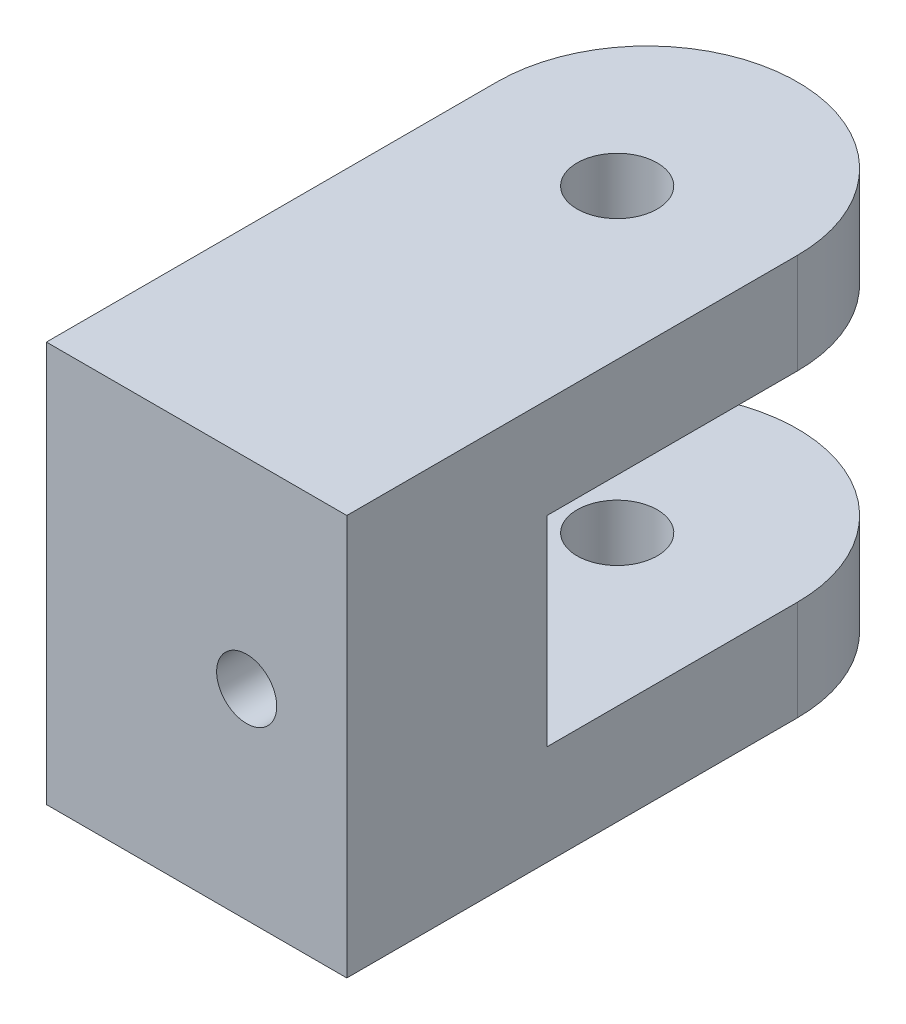
SolidWorks part; units mm, degrees
ref_plane "前视基准面" through (0, 0, 0) normal (0, 0, 1) x (1, 0, 0)
ref_plane "上视基准面" through (0, 0, 0) normal (0, 1, 0) x (1, 0, 0)
ref_plane "右视基准面" through (0, 0, 0) normal (1, 0, 0) x (0, 0, -1)
other "Configuration Table"
sketch "草图1" plane through (0, 0, 0) normal (0, 0, 1) x (1, 0, 0)
  line L1 (0, 0) -> (15, 0)
  line L2 (0, 0) -> (0, 20)
  line L3 (0, 20) -> (15, 20)
  line L4 (15, 0) -> (15, 20)
  point P4 (0, 0)
  dimension "D1" = 15
  dimension "D2" = 20
extrude "凸台-拉伸1" add sketch "草图1" along normal blind 10
sketch "草图2" plane through (0, 0, 0) normal (0, -1, 0) x (1, 0, 0)
  line L6 (0, 0) -> (0, -20)
  line L7 (0, -20) -> (15, -20)
  line L8 (15, -20) -> (15, 0)
  line L9 (15, 0) -> (0, 0)
  circle A0 centre (7.5, -11) radius 2
  dimension "D4" = 4
  dimension "D1" = 20
  dimension "D2" = 9
  dimension "D3" = 7.5
extrude "凸台-拉伸2" add sketch "草图2" against normal up to surface (20 mm away) up to face at (7.5, 20, 5)
sketch "草图3" plane through (15, 0, 0) normal (1, 0, 0) x (0, 0, -1)
  line L0 (20, 20) -> (20, 0) construction
  line L1 (20, 15) -> (0, 15)
  line L2 (20, 15) -> (20, 5)
  line L3 (20, 5) -> (0, 5)
  line L4 (0, 15) -> (0, 5)
  line L5 (-10, 20) -> (20, 20) construction
  dimension "D1" = 10
  dimension "D2" = 5
  dimension "D3" = 20
extrude "切除-拉伸1" cut sketch "草图3" against normal through all
fillet "圆角1" 2 edges at (15, 17.5, -20) (0, 17.5, -20) type full round first side face at (15, 10, -7.5) second side face at (0, 10, -7.5) middle face at (7.5, 17.5, -20)
fillet "圆角2" 2 edges at (15, 2.5, -20) (0, 2.5, -20) type full round first side face at (15, 10, -5.625) second side face at (0, 10, -5.625) middle face at (7.5, 2.5, -20)
sketch "草图4" plane through (0, 0, 10) normal (0, 0, 1) x (1, 0, 0)
  line L0 (0, 20) -> (0, 0) construction
  line L1 (15, 20) -> (0, 20) construction
  circle A0 centre (10, 10) radius 1.5
  dimension "D1" = 3
  dimension "D2" = 10
  dimension "D3" = 10
extrude "切除-拉伸2" cut sketch "草图4" against normal through all
